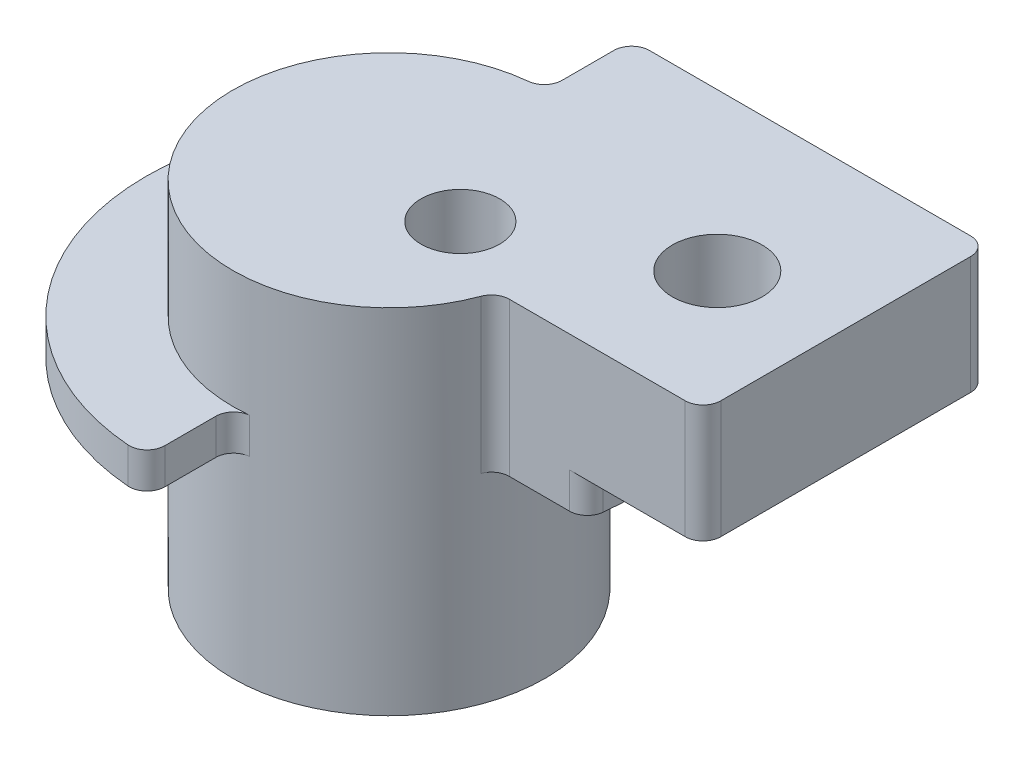
SolidWorks part; units mm, degrees
material "PET"
ref_plane "Front Plane" through (0, 0, 0) normal (1, 0, 0) x (0, 1, 0)
ref_plane "Top Plane" through (0, 0, 0) normal (0, 0, 1) x (0, 1, 0)
ref_plane "Right Plane" through (0, 0, 0) normal (0, 1, 0) x (-1, 0, 0)
sketch "Sketch2" plane through (0, 0, 0) normal (0, 0, 1) x (0, 1, 0)
  line L0 (0, 6.95) -> (0, -6.95) construction
  line L1 (15.7163, -6.95) -> (-15.7163, -6.95)
  line L2 (15.7163, -6.95) -> (15.7163, 6.95)
  line L3 (15.7163, 6.95) -> (-15.7163, 6.95)
  line L4 (-15.7163, -6.95) -> (-15.7163, 6.95)
  line L5 (15.7163, -6.95) -> (-15.7163, 6.95) construction
  line L6 (15.7163, 6.95) -> (-15.7163, -6.95) construction
  line L11 (-10.4775, 10.795) -> (-8.89, 10.795)
  line L12 (-10.4775, 10.795) -> (-10.4775, -10.795)
  line L19 (-10.4775, -10.795) -> (-8.89, -10.795)
  line L20 (-8.89, 10.795) -> (-8.89, -10.795)
  line L21 (10.4775, -10.795) -> (8.89, -10.795)
  line L22 (8.89, 10.795) -> (8.89, -10.795)
  line L23 (10.4775, 10.795) -> (8.89, 10.795)
  line L24 (10.4775, 10.795) -> (10.4775, -10.795)
  line L25 (-15.7163, 0) -> (15.7163, 0)
  point P0 (0, 0)
  point P6 (0, 0)
  point P11 (0, 0)
  point P16 (-10.4775, 0)
  dimension "D1" = 13.9
  dimension "D2" = 31.4325
  dimension "D5" = 1.5875
  dimension "D6" = 21.59
  dimension "D7" = 8.89
revolve "Revolve2" add sketch "Sketch2" angle 360 about L25 region at (-3.475, 13.0969, 0) region at (-3.475, 9.6838, 0) region at (-3.475, 0, 0) region at (-8.8725, 9.6838, 0) region at (-3.475, -9.6838, 0) region at (-3.475, -13.0969, 0) region at (-8.8725, -9.6838, 0)
sketch "Sketch3" plane through (0, 0, 0) normal (0, 1, 0) x (-1, 0, 0)
  circle A0 centre (0, 0) radius 11.3381
extrude "Cut-Extrude1" cut sketch "Sketch3" against normal blind 21.336
sketch "Sketch5" plane through (0, 15.7163, 0) normal (0, 1, 0) x (-1, 0, 0)
  line L5 (0, -10.795) -> (-15.875, -10.795)
  line L6 (0, -10.795) -> (0, 1.905)
  line L7 (0, 1.905) -> (-15.875, 1.905)
  line L8 (-15.875, -10.795) -> (-15.875, 1.905)
  circle A0 centre (-3.175, 0) radius 1.75
  circle A1 centre (0, 0) radius 6.95 construction
  circle A2 centre (0, 0) radius 6.95 construction
  circle A3 centre (-3.175, 0) radius 3.35 construction
  circle A9 centre (0, 0) radius 6.95
  circle A10 centre (-10.795, -3.81) radius 2
  circle A13 centre (0, 0) radius 10.795 construction
  circle A14 centre (-10.795, -3.81) radius 3.6 construction
  circle A15 centre (0, 0) radius 10.541 construction
  point P4 (6.95, 0)
  point P13 (-3.175, 1.75)
  point P15 (-3.175, 3.35)
  point P20 (-8.795, -3.81)
  point P21 (-7.195, -3.81)
  circle M7 centre (0, 0) radius 6.95
  dimension "D1" = 3.5
  dimension "D8" = 1.6
  dimension "D3" = 4
  dimension "D7" = 15.875
  dimension "D10" = 21.082
  dimension "D2" = 3.175
  dimension "D4" = 7.62
  dimension "D5" = 1.6
  dimension "D6" = 12.7
  dimension "D9" = 3.81
  dimension "5" = 0
extrude "Cut-Extrude3" cut sketch "Sketch5" against normal blind 27.432 contours A0 region at (3.175, 15.7163, 0)
extrude "Boss-Extrude2" add sketch "Sketch5<3>" against normal up to surface (5.2387 mm away) contours L8 A10 M7 region at (9.4749, 15.7163, -5.4243) up to face at (6.95, 10.4775, 0)
sketch "Sketch5<3>" plane through (0, 15.7163, 0) normal (0, 1, 0) x (-1, 0, 0) same geometry as "Sketch5"
fillet "Fillet1" radius 0.7937 5 edges at (0, 13.0969, -10.795) (0, 13.0969, -6.95) (15.875, 13.0969, -10.795) (6.6838, 13.0969, 1.905) (15.875, 13.0969, 1.905)
sketch "Sketch6" plane through (0, 10.4775, 0) normal (0, 1, 0) x (-1, 0, 0)
  line L0 (0, 6.95) -> (0, 10.795)
  line L3 (0, -7.703) -> (0, -10.0013)
  line L4 (-10.6256, 1.905) -> (-7.2583, 1.905)
  line L5 (0, -7.703) -> (0, -10.0013)
  line L6 (-10.6256, 1.905) -> (-7.2583, 1.905)
  arc A0 (0.7124, -6.9134) -> (-6.5143, 2.4221) centre (0, 0) ccw construction
  arc A1 (-0.6251, -10.7769) -> (-10.6256, 1.905) centre (0, 0) ccw construction
  arc A7 (0.7124, -6.9134) -> (-6.5143, 2.4221) centre (0, 0) ccw
  arc A8 (0.7124, -6.9134) -> (0, -7.703) centre (0.7938, -7.703) ccw
  arc A9 (-0.6251, -10.7769) -> (0, -10.0013) centre (-0.7937, -10.0013) ccw
  arc A10 (-0.6251, -10.7769) -> (-10.6256, 1.905) centre (0, 0) ccw
  arc A11 (-7.2583, 1.905) -> (-6.5143, 2.4221) centre (-7.2583, 2.6987) ccw
  arc A12 (0.7124, -6.9134) -> (-6.5143, 2.4221) centre (0, 0) ccw
  arc A13 (0.7124, -6.9134) -> (0, -7.703) centre (0.7938, -7.703) ccw
  arc A14 (-0.6251, -10.7769) -> (0, -10.0013) centre (-0.7937, -10.0013) ccw
  arc A15 (-0.6251, -10.7769) -> (-10.6256, 1.905) centre (0, 0) ccw
  arc A16 (-7.2583, 1.905) -> (-6.5143, 2.4221) centre (-7.2583, 2.6987) ccw
  arc M8 (-6.5143, 2.4221) -> (0.7124, -6.9134) centre (0, 0) cw
  arc M12 (-0.6251, -10.7769) -> (-10.6256, 1.905) centre (0, 0) ccw
  line M13 (-10.6256, 1.905) -> (-7.2583, 1.905)
  arc M14 (-7.2583, 1.905) -> (-6.5143, 2.4221) centre (-7.2583, 2.6987) ccw
  dimension "D1" = 0
extrude "Cut-Extrude4" cut sketch "Sketch6" against normal blind 14.224 contours L0 M8 M12 M13 M14 region at (5.2452, 10.4775, 6.5067)
fillet "Fillet2" radius 0.7937 3 edges at (10.6256, 9.6838, 1.905) (0, 9.6838, 6.95) (0, 9.6838, 10.795)
